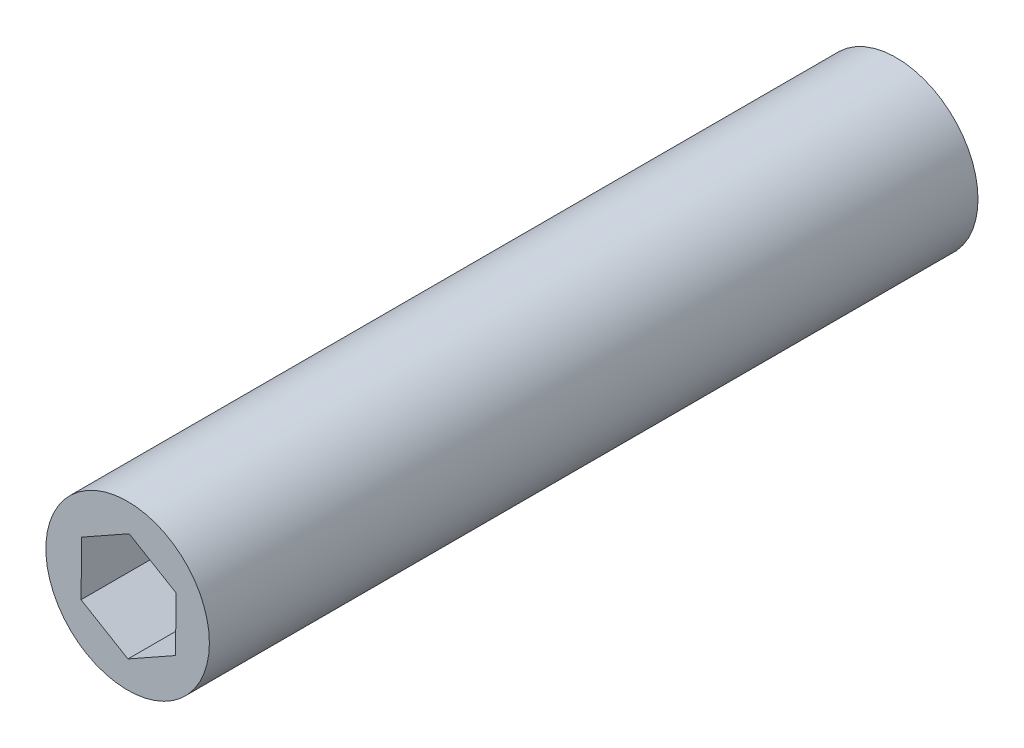
SolidWorks part; units mm, degrees
material "7075-T6 (SN)"
ref_plane "Front Plane" through (0, 0, 0) normal (0, 0, 1) x (1, 0, 0)
ref_plane "Top Plane" through (0, 0, 0) normal (0, 1, 0) x (1, 0, 0)
ref_plane "Right Plane" through (0, 0, 0) normal (1, 0, 0) x (0, 0, -1)
sketch "Sketch1" plane through (0, 0, 0) normal (0, 0, 1) x (1, 0, 0)
  circle A0 centre (-45.3853, 54.654) radius 15
extrude "Extrude1" add sketch "Sketch1" along normal blind 141
sketch "Sketch2" plane through (0, 0, 141) normal (0, 0, 1) x (1, 0, 0)
  line L0 (-45.0329, 69.6498) -> (-45.3853, 39.654) construction
  line L1 (-60.3853, 54.654) -> (-30.3853, 54.654) construction
  line L3 (-45.0916, 64.6569) -> (-53.8132, 59.7572)
  line L4 (-53.8132, 59.7572) -> (-53.9307, 49.7543)
  line L5 (-53.9307, 49.7543) -> (-45.3266, 44.651)
  line L6 (-45.3266, 44.651) -> (-36.6051, 49.5507)
  line L7 (-36.6051, 49.5507) -> (-36.4876, 59.5537)
  line L8 (-36.4876, 59.5537) -> (-45.0916, 64.6569)
  circle A0 centre (-45.3853, 54.654) radius 15 construction
  circle A1 centre (-45.2091, 54.654) radius 8.6634 construction
ref_point "Point1"
extrude "Extrude2" cut sketch "Sketch2" against normal blind 30
sketch "Sketch5" plane through (0, 0, 0) normal (0, 0, -1) x (-1, 0, 0)
  line L0 (30.3853, 54.654) -> (60.3853, 54.654) construction
  line L1 (45.3853, 69.654) -> (45.3853, 39.654) construction
  line L3 (45.3853, 64.6546) -> (36.7245, 59.6543)
  line L4 (36.7245, 59.6543) -> (36.7245, 49.6537)
  line L5 (36.7245, 49.6537) -> (45.3853, 44.6533)
  line L6 (45.3853, 44.6533) -> (54.0461, 49.6537)
  line L7 (54.0461, 49.6537) -> (54.0461, 59.6543)
  line L8 (54.0461, 59.6543) -> (45.3853, 64.6546)
  circle A0 centre (45.3853, 54.654) radius 15 construction
  circle A1 centre (45.3853, 54.654) radius 8.6608 construction
ref_point "Point3"
extrude "Extrude3" cut sketch "Sketch5" against normal blind 30
shell "Shell5" thickness 2 removed face at (-45.3853, 54.654, 30)
sketch "Sketch6" plane through (0, 0, 30) normal (0, 0, 1) x (1, 0, 0)
  line L1 (-34.7245, 60.809) -> (-45.2972, 66.8114)
  line L2 (-45.2972, 66.8114) -> (-55.7818, 60.6564)
  line L3 (-55.7818, 60.6564) -> (-55.6937, 48.499)
  line L4 (-55.6937, 48.499) -> (-45.121, 42.4966)
  line L5 (-45.121, 42.4966) -> (-34.6364, 48.6516)
  line L6 (-34.6364, 48.6516) -> (-34.7245, 60.809)
  circle A0 centre (-45.2091, 54.654) radius 10.5289 construction
extrude "Extrude4" add sketch "Sketch6" along normal blind 2
